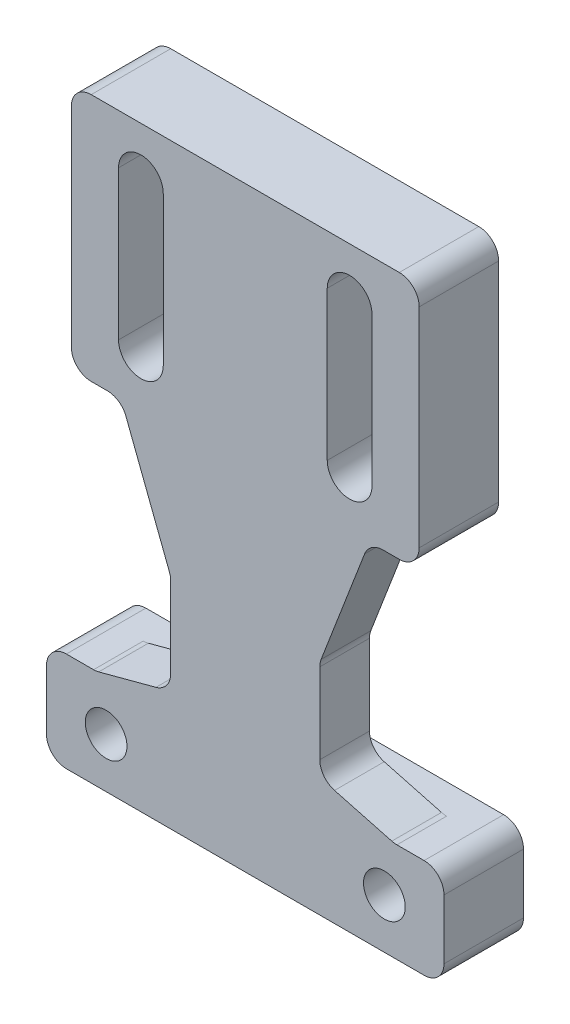
SolidWorks part; units mm, degrees
ref_plane "Спереди" through (0, 0, 0) normal (0, 0, 1) x (1, 0, 0)
ref_plane "Сверху" through (0, 0, 0) normal (0, 1, 0) x (1, 0, 0)
ref_plane "Справа" through (0, 0, 0) normal (1, 0, 0) x (0, 0, -1)
sketch "Эскиз2" plane through (0, 0, 0) normal (0, 0, 1) x (1, 0, 0)
  line L0 (0, 0) -> (40, 0)
  line L1 (40, 0) -> (40, 10)
  line L2 (2.5, 35) -> (7.5, 35)
  line L3 (27.5, 12) -> (27.5, 22)
  line L5 (37.5, 35) -> (37.5, 60)
  line L6 (37.5, 60) -> (2.5, 60)
  line L7 (2.5, 60) -> (2.5, 35)
  line L9 (12.5, 22) -> (12.5, 12)
  line L10 (40, 10) -> (35, 10)
  line L11 (0, 10) -> (0, 0)
  line L12 (20, 0) -> (20, 8.8621) construction
  line L13 (0, 10) -> (5, 10)
  line L14 (5, 10) -> (12.5, 12)
  line L15 (35, 10) -> (27.5, 12)
  line L16 (7.5, 35) -> (12.5, 22)
  line L17 (27.5, 22) -> (32.5, 35)
  line L18 (32.5, 35) -> (37.5, 35)
  dimension "D1" = 35
  dimension "D2" = 40
  dimension "D3" = 15
  dimension "D4" = 12.5
  dimension "D5" = 10
  dimension "D6" = 12
  dimension "D7" = 35
  dimension "D8" = 10
  dimension "D9" = 17.5
  dimension "D10" = 25
  dimension "D11" = 5
  dimension "D12" = 5
  dimension "D13" = 5
  dimension "D14" = 5
extrude "Бобышка-Вытянуть1" add sketch "Эскиз2" along normal blind 8
fillet "Скругление3" radius 2 16 edges at (0, 0, 4) (40, 0, 4) (37.5, 60, 4) (2.5, 60, 4) (32.5, 35, 4) (27.5, 22, 4) (27.5, 12, 4) (12.5, 12, 4) (12.5, 22, 4) (7.5, 35, 4) (2.5, 35, 4) (37.5, 35, 4) (0, 10, 4) (5, 10, 4) (35, 10, 4) (40, 10, 4)
sketch "Эскиз3" plane through (0, 0, 0) normal (0, 0, -1) x (-1, 0, 0)
  line L6 (-20, 0) -> (-20, 41.2869) construction
  line L7 (-2, 0) -> (-38, 0) construction
  line L9 (-45, 35) -> (5, 35)
  line L10 (-45, 35) -> (-45, 10)
  line L11 (-45, 10) -> (5, 10)
  line L12 (5, 35) -> (5, 10)
  line L13 (-45, 35) -> (5, 10) construction
  line L14 (-45, 10) -> (5, 35) construction
  point P4 (-20, 22.5)
  dimension "D1" = 10
  dimension "D2" = 50
  dimension "D3" = 25
extrude "Вырез-Вытянуть1" cut sketch "Эскиз3" against normal blind 3
sketch "Эскиз5" plane through (0, 0, 0) normal (0, 0, -1) x (-1, 0, 0)
  line L0 (0, 5) -> (-40, 5) construction
  line L1 (0, 8) -> (0, 2) construction
  line L2 (-40, 2) -> (-40, 8) construction
  line L3 (-34, 10) -> (-34, 0) construction
  line L5 (-2, 0) -> (-38, 0) construction
  line L6 (-6, 10) -> (-6, 0) construction
  dimension "D1" = 6
  dimension "D2" = 6
hole_wizard "Отверстие обработанное метчиком M5x0.81" positions "Эскиз7" profile "Эскиз6" tap size "M5x0.8" standard "Ansi Metric" end condition through all
sketch "Эскиз7" plane through (0, 0, 0) normal (0, 0, -1) x (-1, 0, 0)
  line L0 (-34, 10) -> (-34, 0) construction
  line L1 (-6, 10) -> (-6, 0) construction
  point P0 (-34, 5)
  point P4 (-6, 5)
sketch "Эскиз6" plane through (34, 5, 0) normal (1, 0, 0) x (0, 1, 0)
  line L0 (0, 0) -> (0, 8)
  line L1 (0, 8) -> (2.1, 8)
  line L2 (2.1, 8) -> (2.1, 0)
  line L5 (2.1, 0) -> (0, 0)
  line L11 (0, -6.35) -> (0, 107.95) construction
  dimension "Диаметр проходного сверла" = 4.2
  dimension "Глубина проходного сверла" = 8
cosmetic thread "Отверстие резьбы1" parameters "D2"=5
cosmetic thread "Отверстие резьбы2" parameters "D2"=5
sketch "Эскиз8" plane through (0, 0, 0) normal (0, 0, -1) x (-1, 0, 0)
  line L0 (-30.5, 60) -> (-30.5, 35) construction
  line L1 (-35.5, 60) -> (-4.5, 60) construction
  line L4 (-30.5, 55) -> (-30.5, 40) construction
  line L5 (-28.25, 55) -> (-28.25, 40)
  line L6 (-32.75, 55) -> (-32.75, 40)
  line L7 (-20, 60) -> (-20, 50) construction
  line L8 (-9.5, 55) -> (-9.5, 40) construction
  line L9 (-11.75, 55) -> (-11.75, 40)
  line L10 (-7.25, 55) -> (-7.25, 40)
  line L11 (-37.5, 37) -> (-37.5, 58) construction
  line L12 (-4.5, 35) -> (-35.5, 35) construction
  arc A0 (-28.25, 55) -> (-32.75, 55) centre (-30.5, 55) ccw
  arc A1 (-32.75, 40) -> (-28.25, 40) centre (-30.5, 40) ccw
  arc A2 (-11.75, 55) -> (-7.25, 55) centre (-9.5, 55) cw
  arc A3 (-7.25, 40) -> (-11.75, 40) centre (-9.5, 40) cw
  point P10 (-30.5, 47.5)
  point P19 (-9.5, 47.5)
  dimension "D2" = 2.25
  dimension "D1" = 7
  dimension "D3" = 15
  dimension "D4" = 5
extrude "Вырез-Вытянуть3" cut sketch "Эскиз8" against normal through all
